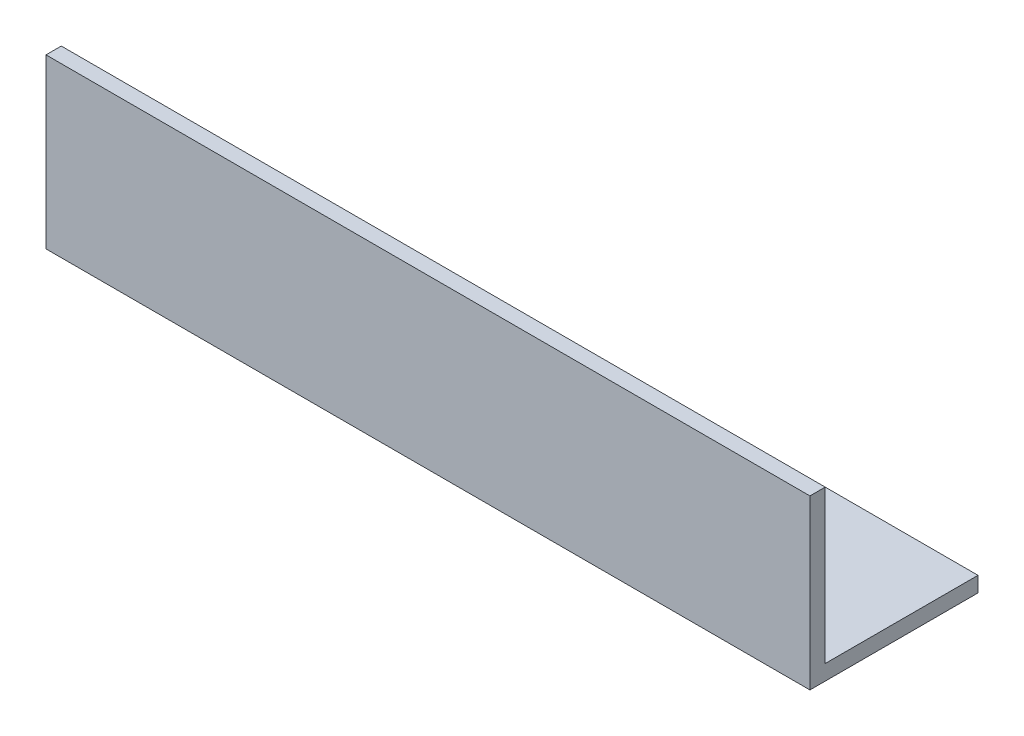
SolidWorks part; units mm, degrees
ref_plane "Спереди" through (0, 0, 0) normal (0, 0, 1) x (1, 0, 0)
ref_plane "Сверху" through (0, 0, 0) normal (0, 1, 0) x (1, 0, 0)
ref_plane "Справа" through (0, 0, 0) normal (1, 0, 0) x (0, 0, -1)
sketch "Эскиз1" plane through (0, 0, 0) normal (1, 0, 0) x (0, 0, -1)
  line L0 (0, 0) -> (0, 30)
  line L1 (0, 0) -> (30, 0)
extrude "Вытянуть-Тонкостенный1" add sketch "Эскиз1" along normal blind 150 thin thin type one direction wall 3
sketch "Эскиз2" plane through (0, -3, 0) normal (0, -1, 0) x (1, 0, 0)
  line L0 (75, -34.5488) -> (75, 3.8648) construction
  circle A0 centre (130, -9) radius 5
  circle A1 centre (100, -9) radius 5
  circle A2 centre (50, -9) radius 5
  circle A3 centre (20, -9) radius 5
  dimension "D1" = 2
extrude "Вырез-Вытянуть1" cut sketch "Эскиз2" against normal through all
